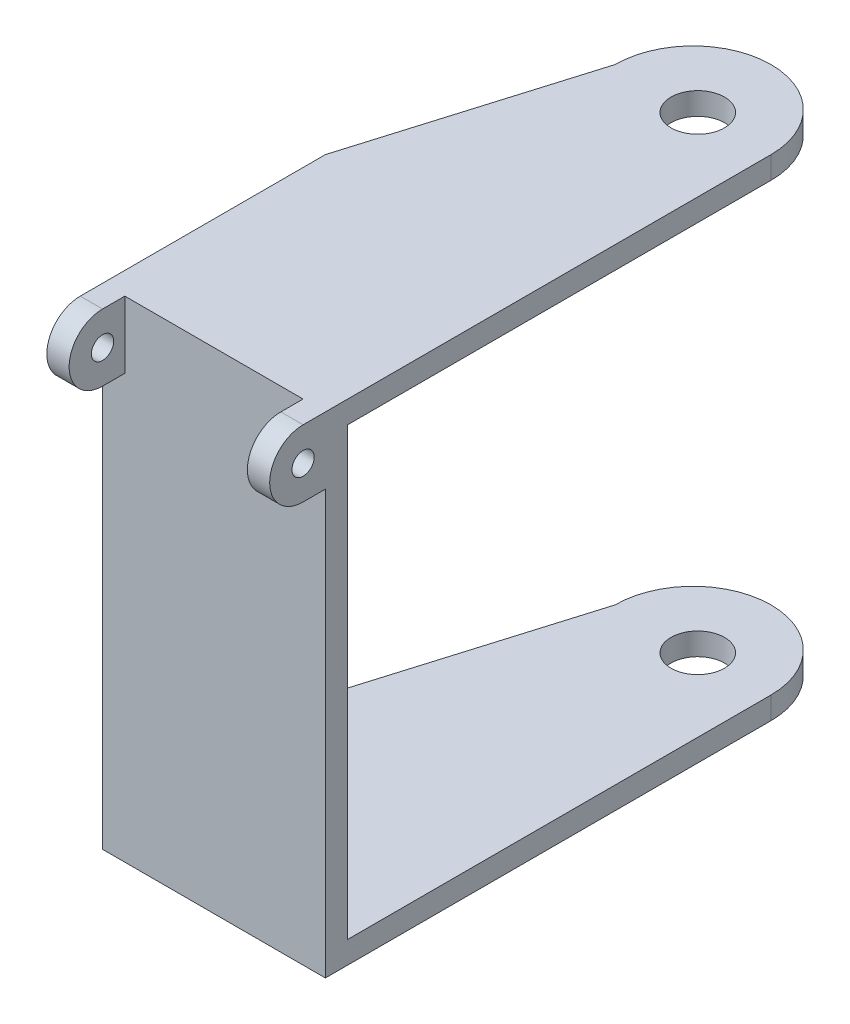
SolidWorks part; units mm, degrees
ref_plane "前视基准面" through (0, 0, 0) normal (0, 0, 1) x (1, 0, 0)
ref_plane "上视基准面" through (0, 0, 0) normal (0, 1, 0) x (1, 0, 0)
ref_plane "右视基准面" through (0, 0, 0) normal (1, 0, 0) x (0, 0, -1)
other "Configuration Table"
sketch "草图1" plane through (0, 0, 0) normal (0, 0, 1) x (1, 0, 0)
  point P0 (-1.7813, 45.6727)
sketch "草图2" plane through (0, 0, 0) normal (0, 1, 0) x (1, 0, 0)
  line L1 (2.5, -5) -> (-2.5, -5)
  line L2 (2.5, -5) -> (2.5, 5)
  line L3 (2.5, 5) -> (-2.5, 5)
  line L4 (-2.5, -5) -> (-2.5, 5)
  line L5 (2.5, -5) -> (-2.5, 5) construction
  line L6 (2.5, 5) -> (-2.5, -5) construction
  point P0 (0, 0)
  dimension "D1" = 10
  dimension "D2" = 5
extrude "凸台-拉伸1" add sketch "草图2" along normal blind 0.5
sketch "草图3" plane through (0, 0.5, 0) normal (0, 1, 0) x (1, 0, 0)
  line L0 (-2.5, 0) -> (-1, 5)
  line L1 (-2.5, 5) -> (-2.5, -5) construction
  line L2 (2.5, 5) -> (-2.5, 5) construction
  line L4 (-1, 5) -> (-4.5974, 7.1555)
  line L5 (-2.5, 0) -> (-6.0974, 2.1555)
  line L6 (-4.5974, 7.1555) -> (-6.0974, 2.1555)
  dimension "D1" = 1.5
extrude "切除-拉伸1" cut sketch "草图3" against normal blind 1.5
sketch "草图6" plane through (0, 0, 0) normal (0, -1, 0) x (1, 0, 0)
  line L0 (-1, -5) -> (2.5, -5)
  line L1 (2.5, -5) -> (-1, -5) construction
  line L2 (2.5, 5) -> (2.5, -5) construction
  arc A0 (2.5, -5) -> (-1, -5) centre (0.75, -5) cw
extrude "凸台-拉伸3" add sketch "草图6" against normal blind 0.5 contours A0 L0
sketch "草图8" plane through (0, 0.5, 0) normal (0, 1, 0) x (1, 0, 0)
  circle A0 centre (0.8584, 4.9968) radius 0.6
  dimension "D1" = 1.2
extrude "切除-拉伸2" cut sketch "草图8" against normal blind 0.5
sketch "草图10" plane through (-2.5, 0, 0) normal (-1, 0, 0) x (0, 0, 1)
  line L0 (0, 0.25) -> (5, 0.25)
  line L1 (0, 0) -> (0, 0.5) construction
  line L2 (5, 0.5) -> (5, 0) construction
  line L3 (0, 0) -> (5, 0) construction
sketch "草图12" plane through (0, 0, 0) normal (0, -1, 0) x (1, 0, 0)
  line L0 (-2.5, 4.5) -> (-2.5, 5)
  line L1 (-2.5, 4.5) -> (2.5, 4.5)
  line L2 (-2.5, 5) -> (2.5, 5)
  line L3 (2.5, 4.5) -> (2.5, 5)
  line L4 (-2.5, 0) -> (-2.5, 5) construction
  dimension "D1" = 0.5
extrude "凸台-拉伸4" add sketch "草图12" along normal blind 10.5
sketch "草图14" plane through (0, 0, 4.5) normal (0, 0, -1) x (-1, 0, 0)
  line L0 (2.5, -10) -> (2.5, -10.5)
  line L1 (2.5, -10) -> (-2.5, -10)
  line L2 (2.5, -10.5) -> (-2.5, -10.5)
  line L3 (-2.5, -10) -> (-2.5, -10.5)
  line L4 (2.5, -10.5) -> (2.5, 0) construction
  dimension "D1" = 0.5
extrude "凸台-拉伸5" add sketch "草图14" along normal blind 10
sketch "草图16" plane through (0, -10, 0) normal (0, 1, 0) x (1, 0, 0)
  line L0 (-2.5, 5.5) -> (-2.5, 5)
  line L1 (-2.5, 5.5) -> (2.5, 5.5)
  line L2 (-2.5, 5) -> (2.5, 5)
  line L3 (2.5, 5.5) -> (2.5, 5)
  line L4 (-2.5, 5.5) -> (-2.5, -4.5) construction
  dimension "D1" = 0.5
extrude "切除-拉伸3" cut sketch "草图16" against normal blind 10
sketch "草图17" plane through (0, -10, 0) normal (0, 1, 0) x (1, 0, 0)
  line L0 (-1, 5) -> (-2.5, 0)
  line L1 (-1, 5) -> (-3.3607, 6.9503)
  line L2 (-2.5, 0) -> (-4.8607, 1.9503)
  line L3 (-3.3607, 6.9503) -> (-4.8607, 1.9503)
extrude "切除-拉伸4" cut sketch "草图17" against normal blind 10
sketch "草图18" plane through (0, -10, 0) normal (0, 1, 0) x (1, 0, 0)
  line L0 (-1, 5) -> (2.5, 5)
  arc A0 (2.5, 5) -> (-1, 5) centre (0.75, 5) ccw
extrude "凸台-拉伸6" add sketch "草图18" against normal blind 0.5
sketch "草图19" plane through (0, -10, 0) normal (0, 1, 0) x (1, 0, 0)
  circle A0 centre (0.8584, 4.9968) radius 0.6
extrude "切除-拉伸5" cut sketch "草图19" against normal blind 0.5
sketch "草图23" plane through (0, 0, 5) normal (0, 0, 1) x (1, 0, 0)
  line L0 (-2.5, 0.5) -> (2.5, 0.5) construction
  line L1 (2, 0.5) -> (2.5, 0.5)
  line L2 (2, 0.5) -> (2, -1)
  line L3 (2, -1) -> (2.5, -1)
  line L4 (2.5, 0.5) -> (2.5, -1)
  line L5 (2.5, 0.5) -> (2.5, -10.5) construction
  dimension "D1" = 1.5
  dimension "D2" = 0.5
extrude "凸台-拉伸7" add sketch "草图23" along normal blind 0.5
sketch "草图24" plane through (2.5, 0, 0) normal (1, 0, 0) x (0, 0, -1)
  line L0 (-5.5, 0.5) -> (-5.5, -1)
  arc A0 (-5.5, -1) -> (-5.5, 0.5) centre (-5.5, -0.25) cw
extrude "凸台-拉伸9" add sketch "草图24" against normal blind 0.5 contours A0 L0
sketch "草图25" plane through (2.5, 0, 0) normal (1, 0, 0) x (0, 0, -1)
  circle A1 centre (-5.5, -0.25) radius 0.25
  dimension "D1" = 0.5
extrude "切除-拉伸6" cut sketch "草图25" against normal blind 0.5
mirror "镜向1" about plane through (0, 0, 0) normal (1, 0, 0) of "凸台-拉伸7", "凸台-拉伸9"
sketch "草图28" plane through (-2.5, 0, 0) normal (-1, 0, 0) x (0, 0, 1)
  circle A0 centre (5.5, -0.25) radius 0.25
  dimension "D1" = 0.5
extrude "切除-拉伸7" cut sketch "草图28" against normal blind 0.5
equation "\"0.5.00mm\"=1"
